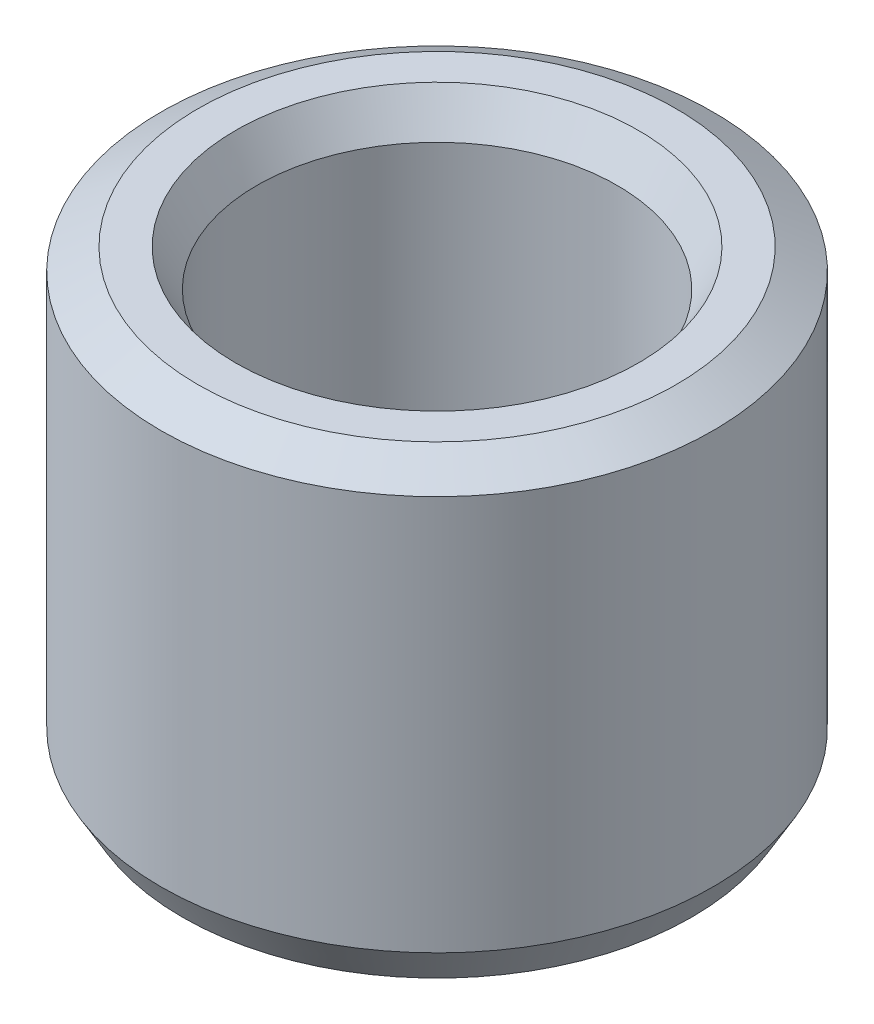
SolidWorks part; units mm, degrees
ref_plane "Front Plane" through (0, 0, 0) normal (0, 0, 1) x (1, 0, 0)
ref_plane "Top Plane" through (0, 0, 0) normal (0, 1, 0) x (1, 0, 0)
ref_plane "Right Plane" through (0, 0, 0) normal (1, 0, 0) x (0, 0, -1)
sketch "Sketch1" plane through (0, 0, 0) normal (0, 1, 0) x (1, 0, 0)
  circle A0 centre (0, 0) radius 47.5
  dimension "SLEEVE_OD" = 95
extrude "Boss-Extrude1" add sketch "Sketch1" along normal blind 78.0126
sketch "Sketch2" plane through (0, 0, 0) normal (0, 1, 0) x (1, 0, 0)
  circle A0 centre (0, 0) radius 30.9962
  dimension "BORE_D" = 61.9923
extrude "Cut-Extrude1" cut sketch "Sketch2" along normal through all
chamfer "Chamfer1" distance 3.6702 angle 60 4 edges at (0, 78.0126, 30.9962) (0, 0, 30.9962) (0, 0, 47.5) (0, 78.0126, 47.5) first distance on face at (0, 78.0126, 30.9962) first distance on face at (0, 0, 30.9962) first distance on face at (0, 78.0126, 47.5)
